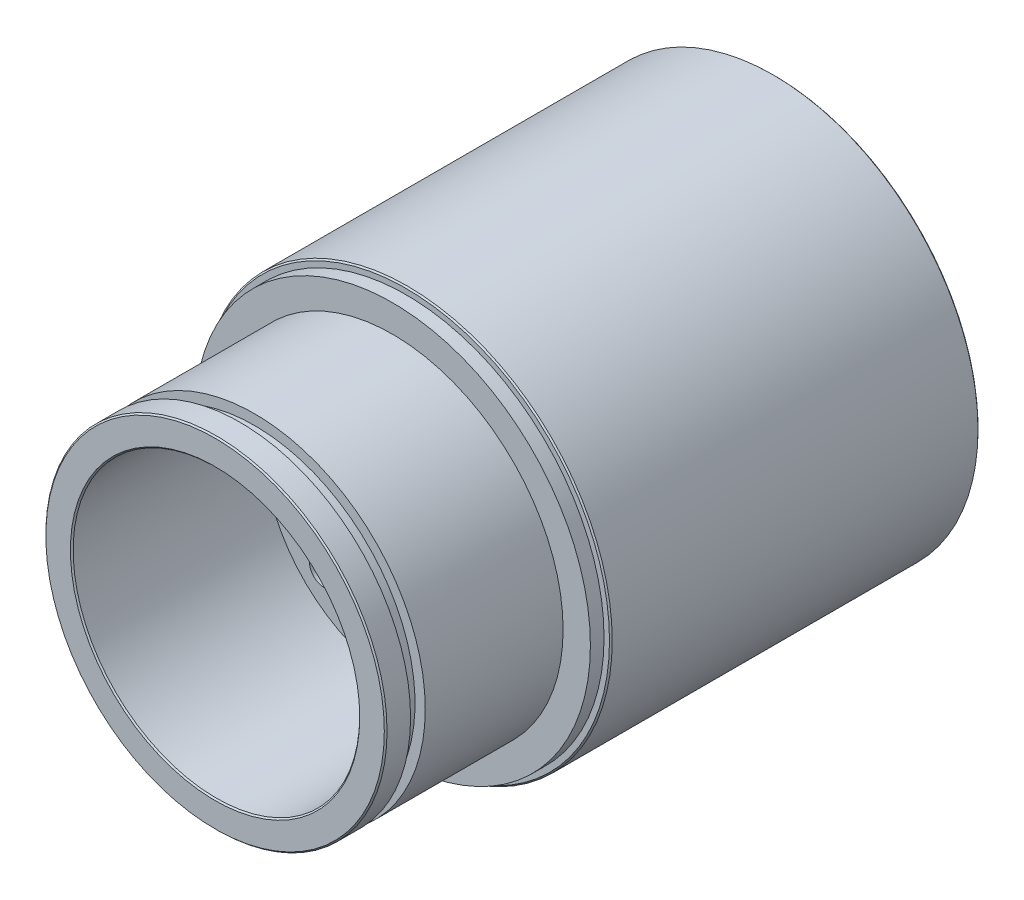
SolidWorks part; units mm, degrees
material "1060 Alloy"
ref_plane "Front Plane" through (0, 0, 0) normal (0, 0, 1) x (1, 0, 0)
ref_plane "Top Plane" through (0, 0, 0) normal (0, 1, 0) x (1, 0, 0)
ref_plane "Right Plane" through (0, 0, 0) normal (1, 0, 0) x (0, 0, -1)
sketch "Sketch1" plane through (0, 0, 0) normal (0, 1, 0) x (1, 0, 0)
  line L0 (0, 0) -> (0, 54) construction
  line L1 (13, 0) -> (21, 0)
  line L2 (21, 0) -> (21, -28)
  line L3 (21, -28) -> (25, -28)
  line L4 (25, -28) -> (25, -2)
  line L5 (29, 0) -> (30, 0)
  line L6 (30, 0) -> (30, 54)
  line L9 (30, 54) -> (20.5, 54)
  line L10 (20.5, 54) -> (20.5, 4)
  line L11 (20.5, 4) -> (13, 4)
  line L12 (13, 4) -> (13, 0)
  line L13 (25, -2) -> (29, -2)
  line L14 (29, -2) -> (29, 0)
  dimension "D1" = 26
  dimension "D2" = 50
  dimension "D3" = 4
  dimension "D4" = 4
  dimension "D5" = 41
  dimension "D6" = 50
  dimension "D7" = 58
  dimension "D10" = 2
  dimension "D11" = 60
  dimension "D12" = 26
revolve "Revolve1" add sketch "Sketch1" angle 360 about L0
sketch "Sketch2" plane through (0, 0, 0) normal (0, 1, 0) x (1, 0, 0)
  line L0 (25, -28) -> (25, -2) construction
  line L1 (25, -22.2) -> (23.5, -22.2)
  line L2 (25, -22.2) -> (25, -24.35)
  line L3 (25, -24.35) -> (23.5, -24.35)
  line L4 (23.5, -22.2) -> (23.5, -24.35)
  line L5 (0, 0) -> (0, -28) construction
  line L6 (-25, 0) -> (25, 0) construction
  line L7 (-25, -28) -> (25, -28) construction
  line L9 (-29, -2) -> (29, -2) construction
  dimension "D1" = 2.15
  dimension "D2" = 47
  dimension "D3" = 20.2
revolve "Cut-Revolve1" cut sketch "Sketch2" angle 360 about L5
chamfer "Chamfer1" distance 0.2 angle 45 5 edges at (30, 0, 0) (20.5, 0, -54) (25, 0, 28) (21, 0, 28) (30, 0, -54)
hole_wizard "M4 Clearance Hole1" positions "Sketch3" profile "Sketch4" hole size "M4" standard "ISO" end condition through all
sketch "Sketch3" plane through (0, 0, 0) normal (0, 0, 1) x (1, 0, 0)
  line L0 (-12.0208, 12.0208) -> (0, 0) construction
  line L2 (0, 0) -> (0, 8.8626) construction
  point P0 (-12.0208, 12.0208)
  dimension "D1" = 17
  dimension "D2" = 45
sketch "Sketch4" plane through (-12.0208, 12.0208, 0) normal (1, 0, 0) x (0, -1, 0)
  line L0 (0, 0) -> (0, 54)
  line L1 (0, 54) -> (2.15, 54)
  line L2 (2.15, 54) -> (2.15, 0)
  line L5 (2.15, 0) -> (0, 0)
  line L11 (0, -6.35) -> (0, 107.95) construction
  dimension "Thru Hole Dia." = 4.3
  dimension "Thru Hole Depth" = 54
pattern_circular "CirPattern1" count 4 over 360 about axis through (0, 0, 0) along (0, 0, 1) of "M4 Clearance Hole1"
hole_wizard "M4 Tapped Hole1" positions "Sketch8" profile "Sketch9" tap size "M4" standard "ISO"
sketch "Sketch8" plane through (0, 0, -54) normal (0, 0, -1) x (-1, 0, 0)
  point P0 (0, 25)
  dimension "D1" = 25
cosmetic thread "Hole Thread3" parameters "D1"=8, "D2"=4
sketch "Sketch9" plane through (0, 25, -54) normal (1, 0, 0) x (0, 1, 0)
  line L0 (0, 0) -> (0, 11.0914)
  line L1 (0, 11.0914) -> (1.65, 10.1)
  line L2 (1.65, 10.1) -> (1.65, 0)
  line L5 (1.65, 0) -> (0, 0)
  line L10 (0, 11.0914) -> (-1.65, 10.1) construction
  line L11 (0, -6.35) -> (0, 107.95) construction
  dimension "Tap Drill Dia." = 3.3
  dimension "Tap Drill Depth" = 10.1
  dimension "Drill Angle" = 118
pattern_circular "CirPattern3" count 6 over 360 about axis through (0, 0, 0) along (0, 0, 1) of "M4 Tapped Hole1" reverse direction yes
move or copy body "Body-Move/Copy1" [suppressed] bodies to move or copy 109
